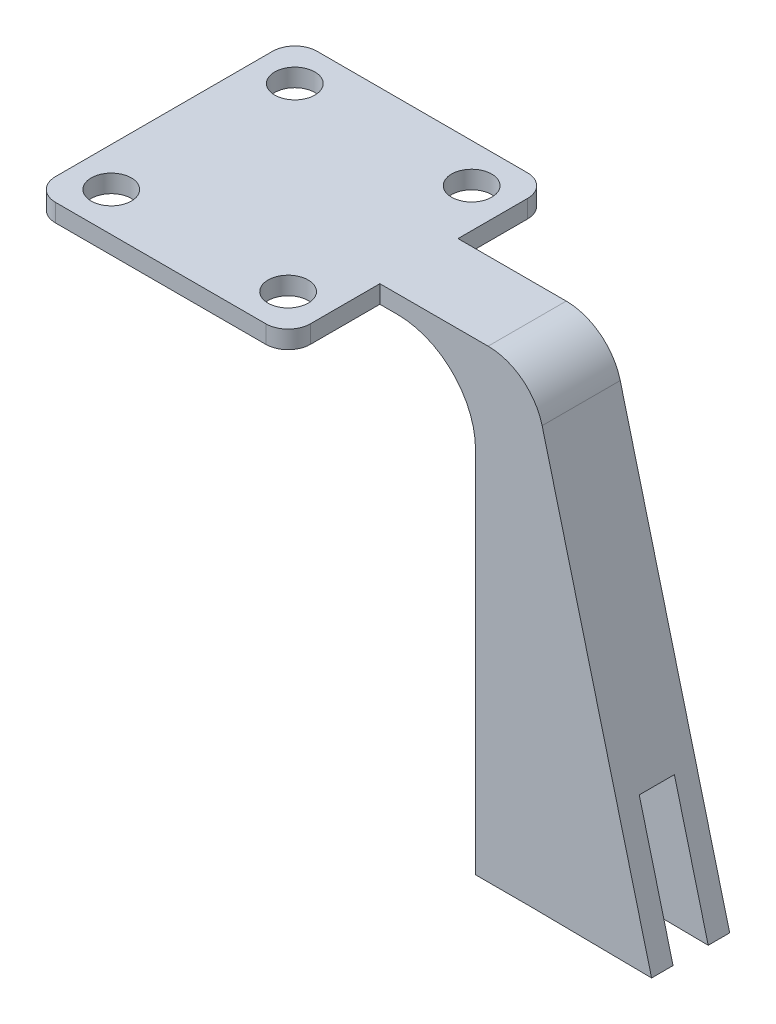
SolidWorks part; units mm, degrees
ref_plane "Front Plane" through (0, 0, 0) normal (0, 0, 1) x (1, 0, 0)
ref_plane "Top Plane" through (0, 0, 0) normal (0, 1, 0) x (1, 0, 0)
ref_plane "Right Plane" through (0, 0, 0) normal (1, 0, 0) x (0, 0, -1)
sketch "Sketch1" plane through (0, 0, 0) normal (0, 1, 0) x (1, 0, 0)
  line L5 (-9.425, -11.725) -> (9.425, -11.725)
  line L6 (-11.425, -9.725) -> (-11.425, 9.725)
  line L7 (-9.425, 11.725) -> (9.425, 11.725)
  line L8 (11.425, -9.725) -> (11.425, 9.725)
  circle A0 centre (-7.925, 8.225) radius 1.8
  arc A1 (-9.425, -11.725) -> (-11.425, -9.725) centre (-9.425, -9.725) cw
  arc A2 (9.425, -11.725) -> (11.425, -9.725) centre (9.425, -9.725) ccw
  arc A3 (9.425, 11.725) -> (11.425, 9.725) centre (9.425, 9.725) cw
  arc A4 (-11.425, 9.725) -> (-9.425, 11.725) centre (-9.425, 9.725) cw
  point P0 (0, 0)
  point P1 (0, 0)
  point P13 (11.425, -11.725)
  point P16 (11.425, 11.725)
  point P19 (-11.425, 11.725)
  dimension "D3" = 3.5
  dimension "D4" = 3.5
  dimension "D5" = 2
  dimension "D1" = 22.85
  dimension "D2" = 23.45
extrude "Boss-Extrude1" add sketch "Sketch1" along normal blind 1.6
sketch "Sketch2" plane through (0, 1.6, 0) normal (0, 1, 0) x (1, 0, 0)
  line L0 (9.425, 11.725) -> (-9.425, 11.725) construction
  line L2 (11.425, -9.725) -> (11.425, 9.725) construction
  line L3 (-9.425, -11.725) -> (9.425, -11.725) construction
  line L4 (-11.425, 9.725) -> (-11.425, -9.725) construction
  circle A0 centre (7.925, 8.225) radius 1.8
  circle A1 centre (-7.925, -8.225) radius 1.8
  circle A2 centre (7.925, -8.225) radius 1.8
  point P8 (0, 0)
  point P10 (11.425, 6.0326)
  point P14 (12.355, -6.6802)
  dimension "D1" = 3.5
  dimension "D2" = 3.5
  dimension "D4" = 3.5
  dimension "D6" = 3.5
  dimension "D3" = 3.5
  dimension "D5" = 3.5
extrude "Cut-Extrude1" cut sketch "Sketch2" against normal blind 1.6
sketch "Sketch3" plane through (0, 1.6, 0) normal (0, 1, 0) x (1, 0, 0)
  line L1 (0, 3.5) -> (25, 3.5)
  line L2 (0, 3.5) -> (0, -3.5)
  line L3 (0, -3.5) -> (25, -3.5)
  line L4 (25, 3.5) -> (25, -3.5)
  dimension "D1" = 25
  dimension "D2" = 7
  dimension "D3" = 3.5
extrude "Boss-Extrude2" add sketch "Sketch3" against normal blind 1.6
sketch "Sketch4" plane through (0, 0, 0) normal (0, -1, 0) x (1, 0, 0)
  line L0 (25, -3.5) -> (11.425, -3.5) construction
  line L1 (25, 3.5) -> (20, 3.5)
  line L2 (25, 3.5) -> (25, -3.5)
  line L3 (25, -3.5) -> (20, -3.5)
  line L4 (20, 3.5) -> (20, -3.5)
  dimension "D1" = 5
extrude "Boss-Extrude3" add sketch "Sketch4" along normal blind 40
fillet "Fillet1" radius 7 1 edges at (20, 0, 0)
sketch "Sketch7" plane through (0, 0, 3.5) normal (0, 0, 1) x (1, 0, 0)
  line L0 (25, 1.6) -> (35.7791, -40.1199)
  line L3 (25, 1.6) -> (25, -40)
  line L4 (25, -40) -> (35.7791, -40.1199)
extrude "Boss-Extrude4" add sketch "Sketch7" against normal blind 7
fillet "Fillet2" radius 5 1 edges at (25, 1.6, 0)
sketch "Sketch10" plane through (-0.4418, -39.717, 0) normal (-0.0111, -0.9999, 0) x (0.9999, -0.0111, 0)
  line L0 (25.4434, 3.5) -> (36.2232, 3.5) construction
  line L1 (19.6442, -1.575) -> (39.6655, -1.575)
  line L2 (19.6442, -1.575) -> (19.6442, 1.575)
  line L3 (19.6442, 1.575) -> (39.6655, 1.575)
  line L4 (39.6655, -1.575) -> (39.6655, 1.575)
  line L5 (19.6442, -1.575) -> (39.6655, 1.575) construction
  line L6 (19.6442, 1.575) -> (39.6655, -1.575) construction
  point P0 (29.6548, 0)
  dimension "D1" = 3.15
  dimension "D2" = 1.925
extrude "Cut-Extrude4" cut sketch "Sketch10" against normal blind 11.7
sketch "Sketch11" plane through (0, -40, 0) normal (0, -1, 0) x (1, 0, 0)
  line L0 (20, 3.5) -> (20, -3.5) construction
  line L1 (25, 1.575) -> (20, 1.575)
  line L2 (25, 1.575) -> (25, -1.575)
  line L3 (25, -1.575) -> (20, -1.575)
  line L4 (20, 1.575) -> (20, -1.575)
  dimension "D1" = 3.15
extrude "Cut-Extrude5" cut sketch "Sketch11" against normal blind 11.7
